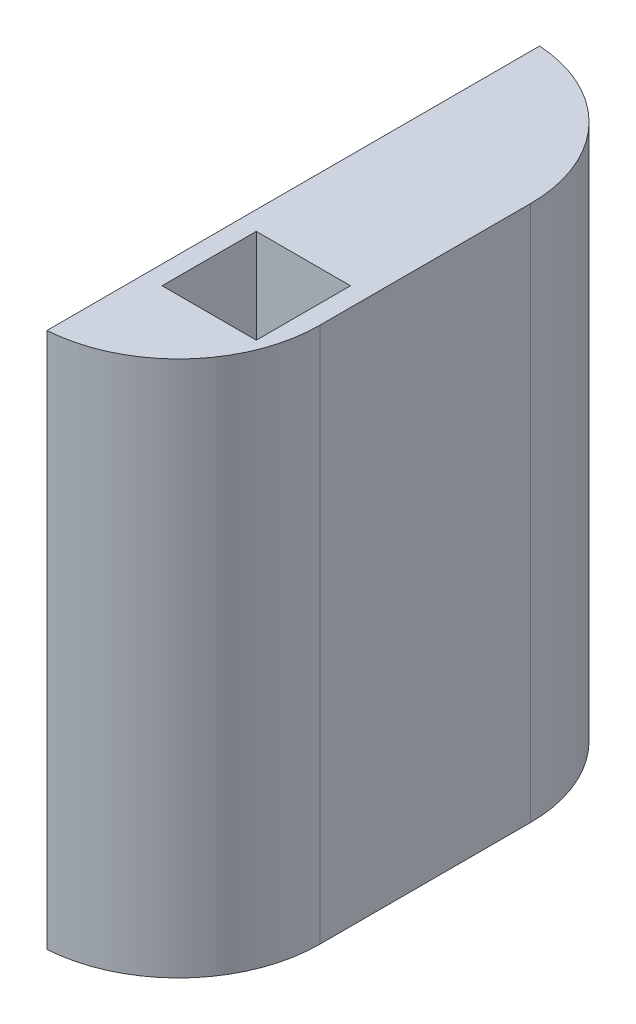
SolidWorks part; units mm, degrees
ref_plane "Спереди" through (0, 0, 0) normal (0, 0, 1) x (1, 0, 0)
ref_plane "Сверху" through (0, 0, 0) normal (0, 1, 0) x (1, 0, 0)
ref_plane "Справа" through (0, 0, 0) normal (1, 0, 0) x (0, 0, -1)
sketch "Эскиз2" plane through (0, 0, 0) normal (0, 1, 0) x (1, 0, 0)
  line L1 (-7, 26.15) -> (7, 26.15)
  line L2 (-7, 26.15) -> (-7, -26.15)
  line L3 (-7, -26.15) -> (7, -26.15)
  line L4 (7, 26.15) -> (7, -26.15)
  line L5 (-7, 26.15) -> (7, -26.15) construction
  line L6 (-7, -26.15) -> (7, 26.15) construction
  point P0 (0, 0)
extrude "Бобышка-Вытянуть1" add sketch "Эскиз2" along normal blind 56.9
sketch "Эскиз3" plane through (0, 56.9, 0) normal (0, 1, 0) x (1, 0, 0)
  line L0 (0, -26.15) -> (0, 26.15)
  line L2 (-7, -26.15) -> (7, -26.15) construction
  line L4 (7, 26.15) -> (-7, 26.15) construction
  line L5 (-7, -26.15) -> (-7, -10.93)
  line L6 (-7, 26.15) -> (-7, -26.15) construction
  line L7 (-7, -10.93) -> (7, -10.93)
  line L8 (7, -26.15) -> (7, 26.15) construction
  line L10 (-5, -5.93) -> (5, -5.93)
  line L11 (-5, -5.93) -> (-5, -15.93)
  line L12 (-5, -15.93) -> (5, -15.93)
  line L13 (5, -5.93) -> (5, -15.93)
  line L14 (-5, -5.93) -> (5, -15.93) construction
  line L15 (-5, -15.93) -> (5, -5.93) construction
  point P13 (0, -10.93)
extrude "Вырез-Вытянуть1" cut sketch "Эскиз3" against normal blind 56.9 contours L11 L12 L0 L7 | L10 L11 L7 L0 | L13 L10 L0 L7 | L13 L7 L0 L12 region at (-2.5, 56.9, 13.43) region at (2.5, 56.9, 13.43) region at (-2.5, 56.9, 8.43) region at (2.5, 56.9, 8.43)
fillet "Скругление2" radius 15 1 edges at (7, 28.45, 26.15)
fillet "Скругление3" radius 15 1 edges at (7, 28.45, -26.15)
